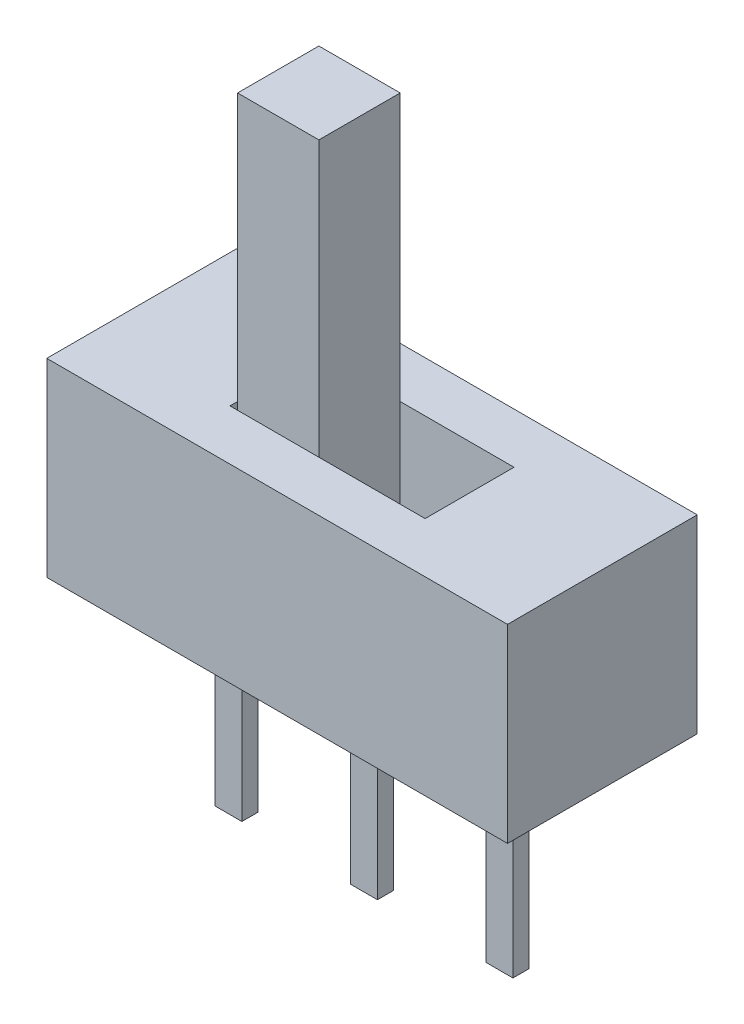
SolidWorks part; units mm, degrees
ref_plane "Front Plane" through (0, 0, 0) normal (0, 0, 1) x (1, 0, 0)
ref_plane "Top Plane" through (0, 0, 0) normal (0, 1, 0) x (1, 0, 0)
ref_plane "Right Plane" through (0, 0, 0) normal (1, 0, 0) x (0, 0, -1)
sketch "Sketch1" plane through (0, 0, 0) normal (0, 1, 0) x (1, 0, 0)
  line L1 (-4.25, 1.75) -> (4.25, 1.75)
  line L2 (-4.25, 1.75) -> (-4.25, -1.75)
  line L3 (-4.25, -1.75) -> (4.25, -1.75)
  line L4 (4.25, 1.75) -> (4.25, -1.75)
  line L5 (0, -1.75) -> (0, 1.75) construction
  line L6 (-4.25, 0) -> (4.25, 0) construction
  point P0 (0, 0)
  dimension "D1" = 8.5
  dimension "D2" = 3.5
extrude "Boss-Extrude1" add sketch "Sketch1" along normal blind 3.5
sketch "Sketch2" plane through (0, 3.5, 0) normal (0, 1, 0) x (1, 0, 0)
  line L0 (0, -2.975) -> (0, 2.975) construction
  line L1 (-1.8, 0.82) -> (1.8, 0.82)
  line L2 (-1.8, 0.82) -> (-1.8, -0.82)
  line L3 (-1.8, -0.82) -> (1.8, -0.82)
  line L4 (1.8, 0.82) -> (1.8, -0.82)
  line L5 (-4.675, 0) -> (4.675, 0) construction
  point P0 (0, 0.82)
  point P6 (-1.8, 0)
  dimension "D1" = 1.64
  dimension "D2" = 3.6
extrude "Cut-Extrude1" cut sketch "Sketch2" against normal blind 2
sketch "Sketch3" plane through (0, 1.5, 0) normal (0, 1, 0) x (1, 0, 0)
  line L0 (-4.675, 0) -> (4.675, 0) construction
  line L5 (-1.73, 0.75) -> (-0.23, 0.75)
  line L6 (-1.73, 0.75) -> (-1.73, -0.75)
  line L7 (-1.73, -0.75) -> (-0.23, -0.75)
  line L8 (-0.23, 0.75) -> (-0.23, -0.75)
  line L9 (-0.98, -0.75) -> (-0.98, 0.75) construction
  line L10 (-1.73, 0) -> (-0.23, 0) construction
  line L13 (-1.73, 0.75) -> (-1.8, 0.75) construction
  line L15 (-1.8, 0.82) -> (-1.8, -0.82) construction
  line L16 (-1.73, 0.75) -> (-1.73, 0.82) construction
  line L17 (-1.8, 0.82) -> (1.8, 0.82) construction
  point P0 (-0.98, 0)
  dimension "D1" = 1.5
extrude "Boss-Extrude3" add sketch "Sketch3" along normal offset from surface (7 mm away) 5 up to face at (0, 3.5, 0) offset beyond the face yes
sketch "Sketch4" plane through (0, 0, 0) normal (0, -1, 0) x (1, 0, 0)
  line L1 (-0.25, 0.15) -> (0.25, 0.15)
  line L2 (-0.25, 0.15) -> (-0.25, -0.15)
  line L3 (-0.25, -0.15) -> (0.25, -0.15)
  line L4 (0.25, 0.15) -> (0.25, -0.15)
  line L5 (0, -0.15) -> (0, 0.15) construction
  line L6 (-0.25, 0) -> (0.25, 0) construction
  point P0 (0, 0)
  dimension "D1" = 0.5
  dimension "D2" = 0.3
extrude "Boss-Extrude4" add sketch "Sketch4" along normal blind 3.7
pattern_linear "LPattern1" count 2 spacing 2.5 along (1, 0, 0) count 2 spacing 2.5 along (-1, 0, 0) of "Boss-Extrude4" pattern seed only yes
equation "\"D1@Boss-Extrude3\" = 2 + 5.5"
